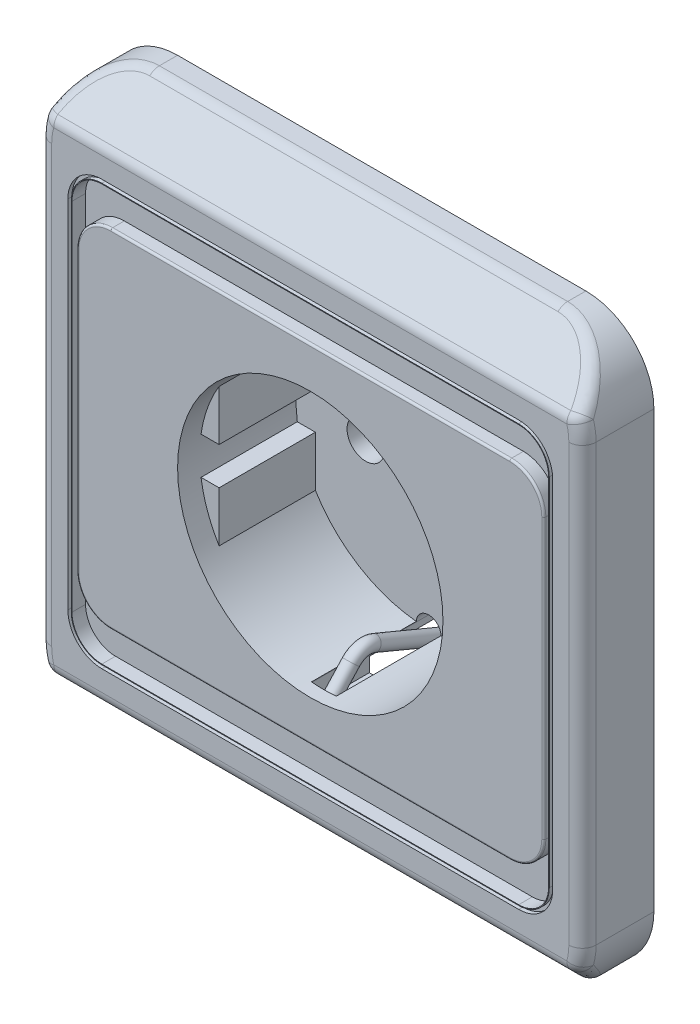
SolidWorks part; units mm, degrees
ref_plane "Ön Düzlem" through (0, 0, 0) normal (0, 0, 1) x (1, 0, 0)
ref_plane "Üst Düzlem" through (0, 0, 0) normal (0, 1, 0) x (1, 0, 0)
ref_plane "Sağ Düzlem" through (0, 0, 0) normal (1, 0, 0) x (0, 0, -1)
sketch "Çizim1" plane through (0, 0, 0) normal (0, 0, 1) x (1, 0, 0)
  line L1 (30, 42) -> (-30, 42)
  line L2 (40, 32) -> (40, -32)
  line L3 (30, -42) -> (-30, -42)
  line L4 (-40, 32) -> (-40, -32)
  line L5 (40, 42) -> (-40, -42) construction
  line L6 (40, -42) -> (-40, 42) construction
  arc A0 (-30, -42) -> (-40, -32) centre (-30, -32) cw
  arc A1 (40, -32) -> (30, -42) centre (30, -32) cw
  arc A2 (30, 42) -> (40, 32) centre (30, 32) cw
  arc A3 (-30, 42) -> (-40, 32) centre (-30, 32) ccw
  point P0 (0, 0)
  dimension "D3" = 10
  dimension "D1" = 84
  dimension "D2" = 80
extrude "Yükseklik-Ekstrüzyon1" add sketch "Çizim1" along normal blind 10.5
sketch "Çizim2" plane through (0, 0, 10.5) normal (0, 0, 1) x (1, 0, 0)
  line L0 (30.625, 30.55) -> (-30.625, 30.55)
  line L1 (30.625, 31.15) -> (-30.625, 31.15)
  line L2 (35.625, 26.15) -> (35.625, -26.15)
  line L3 (30.625, -31.15) -> (-30.625, -31.15)
  line L4 (-35.625, 26.15) -> (-35.625, -26.15)
  line L5 (35.625, 31.15) -> (-35.625, -31.15) construction
  line L6 (35.625, -31.15) -> (-35.625, 31.15) construction
  line L7 (-35.025, 26.15) -> (-35.025, -26.15)
  line L8 (30.625, -30.55) -> (-30.625, -30.55)
  line L9 (35.025, 26.15) -> (35.025, -26.15)
  arc A0 (-30.625, -31.15) -> (-35.625, -26.15) centre (-30.625, -26.15) cw
  arc A1 (35.625, -26.15) -> (30.625, -31.15) centre (30.625, -26.15) cw
  arc A2 (30.625, 31.15) -> (35.625, 26.15) centre (30.625, 26.15) cw
  arc A3 (-30.625, 31.15) -> (-35.625, 26.15) centre (-30.625, 26.15) ccw
  arc A4 (-30.625, 30.55) -> (-35.025, 26.15) centre (-30.625, 26.15) ccw
  arc A5 (-30.625, -30.55) -> (-35.025, -26.15) centre (-30.625, -26.15) cw
  arc A6 (35.025, -26.15) -> (30.625, -30.55) centre (30.625, -26.15) cw
  arc A7 (30.625, 30.55) -> (35.025, 26.15) centre (30.625, 26.15) cw
  point P0 (0, 0)
  dimension "D3" = 5
  dimension "D1" = 62.3
  dimension "D2" = 71.25
  dimension "D4" = 0.6
extrude "Kes-Ekstrüzyon1" cut sketch "Çizim2" against normal blind 0.6
sketch "Çizim3" plane through (0, 0, 10.5) normal (0, 0, 1) x (1, 0, 0)
  line L0 (-35.025, 26.15) -> (-35.025, -26.15) construction
  line L1 (29.325, 25.5) -> (-29.325, 25.5)
  line L2 (34.325, 20.5) -> (34.325, -20.5)
  line L3 (29.325, -25.5) -> (-29.325, -25.5)
  line L4 (-34.325, 20.5) -> (-34.325, -20.5)
  line L5 (34.325, 25.5) -> (-34.325, -25.5) construction
  line L6 (34.325, -25.5) -> (-34.325, 25.5) construction
  line L8 (30.625, 30.55) -> (-30.625, 30.55) construction
  line L9 (30.625, 30.55) -> (-30.625, 30.55)
  line L14 (30.625, 30.55) -> (-30.625, 30.55)
  line L15 (-35.025, 26.15) -> (-35.025, -26.15)
  line L16 (-30.625, -30.55) -> (30.625, -30.55)
  line L17 (35.025, -26.15) -> (35.025, 26.15)
  line L18 (30.625, 30.55) -> (-30.625, 30.55)
  line L19 (-35.025, 26.15) -> (-35.025, -26.15)
  line L20 (-30.625, -30.55) -> (30.625, -30.55)
  line L21 (35.025, -26.15) -> (35.025, 26.15)
  arc A0 (-29.325, -25.5) -> (-34.325, -20.5) centre (-29.325, -20.5) cw
  arc A1 (34.325, -20.5) -> (29.325, -25.5) centre (29.325, -20.5) cw
  arc A2 (29.325, 25.5) -> (34.325, 20.5) centre (29.325, 20.5) cw
  arc A3 (-34.325, 20.5) -> (-29.325, 25.5) centre (-29.325, 20.5) cw
  arc A8 (35.025, 26.15) -> (30.625, 30.55) centre (30.625, 26.15) ccw
  arc A9 (-30.625, 30.55) -> (-35.025, 26.15) centre (-30.625, 26.15) ccw
  arc A10 (-35.025, -26.15) -> (-30.625, -30.55) centre (-30.625, -26.15) ccw
  arc A11 (30.625, -30.55) -> (35.025, -26.15) centre (30.625, -26.15) ccw
  arc A12 (35.025, 26.15) -> (30.625, 30.55) centre (30.625, 26.15) ccw
  arc A13 (-30.625, 30.55) -> (-35.025, 26.15) centre (-30.625, 26.15) ccw
  arc A14 (-35.025, -26.15) -> (-30.625, -30.55) centre (-30.625, -26.15) ccw
  arc A15 (30.625, -30.55) -> (35.025, -26.15) centre (30.625, -26.15) ccw
  point P0 (0, 0)
  arc M9 (35.025, 26.15) -> (30.625, 30.55) centre (30.625, 26.15) ccw
  line M10 (30.625, 30.55) -> (-30.625, 30.55)
  arc M11 (-30.625, 30.55) -> (-35.025, 26.15) centre (-30.625, 26.15) ccw
  line M12 (-35.025, 26.15) -> (-35.025, -26.15)
  arc M13 (-35.025, -26.15) -> (-30.625, -30.55) centre (-30.625, -26.15) ccw
  line M14 (-30.625, -30.55) -> (30.625, -30.55)
  arc M15 (30.625, -30.55) -> (35.025, -26.15) centre (30.625, -26.15) ccw
  line M16 (35.025, -26.15) -> (35.025, 26.15)
  dimension "D3" = 5
  dimension "D1" = 0.7
  dimension "D2" = 51
  dimension "D4" = 0
extrude "Kes-Ekstrüzyon2" cut sketch "Çizim3" against normal blind 2 contours L4 A3 L1 A2 L2 A1 L3 A0 M16 M9 M10 M11 M12 M13 M14 M15 region at (33.079, 28.604, 10.5)
sketch "Çizim4" plane through (0, 0, 10.5) normal (0, 0, 1) x (1, 0, 0)
  circle A0 centre (0, 0) radius 19.5
  dimension "D1" = 39
extrude "Kes-Ekstrüzyon3" cut sketch "Çizim4" against normal blind 51
sketch "Çizim5" plane through (0, 0, 0) normal (0, 0, -1) x (-1, 0, 0)
  circle A0 centre (0, 0) radius 19.5 construction
  circle A1 centre (0, 0) radius 19.5
  circle A2 centre (0, 0) radius 20.5
  dimension "D1" = 1
extrude "Yükseklik-Ekstrüzyon2" add sketch "Çizim5" along normal blind 6.9
sketch "Çizim6" plane through (0, 0, -6.9) normal (0, 0, -1) x (-1, 0, 0)
  circle A1 centre (0, 0) radius 20.5
  circle A2 centre (0, 0) radius 20.5
  dimension "D1" = 0
extrude "Yükseklik-Ekstrüzyon3" add sketch "Çizim6" along normal blind 1
sketch "Çizim7" plane through (0, 0, -6.9) normal (0, 0, 1) x (1, 0, 0)
  line L0 (-16.65, 10.1502) -> (-16.65, 2.75)
  line L1 (-16.65, 2.75) -> (-19.3051, 2.75)
  line L2 (0, 0) -> (0, 14.0864) construction
  line L4 (16.65, 2.75) -> (19.3051, 2.75)
  line L5 (16.65, 10.1502) -> (16.65, 2.75)
  line L6 (-16.65, -2.75) -> (-19.3051, -2.75)
  line L7 (-16.65, -10.1502) -> (-16.65, -2.75)
  line L8 (16.65, -2.75) -> (19.3051, -2.75)
  line L9 (16.65, -10.1502) -> (16.65, -2.75)
  circle A0 centre (0, 0) radius 19.5 construction
  circle A1 centre (0, 0) radius 19.5 construction
  arc A2 (-16.65, 10.1502) -> (-19.3051, 2.75) centre (0, 0) ccw
  arc A3 (16.65, -10.1502) -> (19.3051, -2.75) centre (0, 0) ccw
  arc A4 (19.3051, 2.75) -> (16.65, 10.1502) centre (0, 0) ccw
  arc A5 (-19.3051, -2.75) -> (-16.65, -10.1502) centre (0, 0) ccw
  dimension "D1" = 33.3
extrude "Yükseklik-Ekstrüzyon4" add sketch "Çizim7" along normal blind 14.15
sketch "Çizim8" plane through (0, 0, 10.5) normal (0, 0, 1) x (1, 0, 0)
  line L0 (-1.825, -19.5) -> (-1.825, -22.5)
  line L1 (1.825, -19.5) -> (1.825, -22.5)
  line L2 (1.825, -22.5) -> (-1.825, -22.5)
  line L3 (0, 0) -> (9.3103, 0) construction
  line L4 (0, 0) -> (0, -19.5) construction
  line L5 (1.825, 22.5) -> (-1.825, 22.5)
  line L6 (1.825, 19.5) -> (1.825, 22.5)
  line L7 (-1.825, 19.5) -> (-1.825, 22.5)
  arc A0 (1.825, -19.5) -> (-1.825, -19.5) centre (0, -19.5) ccw
  arc A1 (-16.65, -10.1502) -> (16.65, -10.1502) centre (0, 0) ccw construction
  arc A2 (1.825, 19.5) -> (-1.825, 19.5) centre (0, 19.5) cw
  dimension "D1" = 3.65
  dimension "D2" = 3
extrude "Kes-Ekstrüzyon4" cut sketch "Çizim8" against normal blind 24.15 from offset 2 offset against normal yes
ref_plane "Düzlem1" through (0, 0, 0) normal (-1, 0, 0) x (0, 0, 1)
sketch "Çizim10" plane through (0, 0, 0) normal (-1, 0, 0) x (0, 0, 1)
  line L0 (-8.9, 21.4186) -> (1.161, 17.2265)
  line L1 (4.5224, 17.9644) -> (7.5169, 21.2186)
  line L2 (-7.9, 19.5) -> (-7.9, 17.675) construction
  line L3 (-7.9, 20.4186) -> (0, 20.4186) construction
  arc A0 (1.161, 17.2265) -> (4.5224, 17.9644) centre (2.3148, 19.9958) ccw
  point P9 (3.1, 16.4186)
  dimension "D7" = 3
  dimension "D1" = 1
  dimension "D2" = 1
  dimension "D3" = 110
  dimension "D4" = 5
  dimension "D5" = 12
  dimension "D6" = 4.8
ref_plane "Düzlem2" through (0, 21.2186, 7.5169) normal (0, 0.7359, 0.6771) x (1, 0, 0)
sketch "Çizim11" plane through (0, 21.2186, 7.5169) normal (0, 0.7359, 0.6771) x (1, 0, 0)
  circle A0 centre (0, 0) radius 1
  dimension "D1" = 2
sweep "Süpür1" add profiles "Çizim11" path "Çizim10"
ref_plane "Düzlem3" through (0, 0, 0) normal (0, -1, 0) x (-1, 0, 0)
mirror "Aynalama1" about plane through (0, 0, 0) normal (0, -1, 0) of bodies 109
sketch "Çizim12" plane through (0, 0, -6.9) normal (0, 0, 1) x (1, 0, 0)
  circle A0 centre (9.25, 0) radius 2.75
  circle A1 centre (-9.25, 0) radius 2.75
  point P4 (-6.5, 0)
  point P6 (6.5, 0)
  dimension "D1" = 5.5
  dimension "D2" = 5.5
  dimension "D3" = 13
  dimension "D4" = 6.5
extrude "Kes-Ekstrüzyon5" cut sketch "Çizim12" against normal blind 24.15
sketch "Çizim13" plane through (0, 0, -6.9) normal (0, 0, 1) x (1, 0, 0)
  circle A0 centre (0, 0) radius 2.75
  circle A1 centre (9.25, 0) radius 2.75 construction
extrude "Kes-Ekstrüzyon6" cut sketch "Çizim13" against normal blind 24.15
sketch "Çizim14" plane through (0, 0, -7.9) normal (0, 0, -1) x (-1, 0, 0)
  circle A0 centre (0, 0) radius 2.75 construction
  circle A1 centre (0, 0) radius 2.75 construction
  circle A2 centre (0, 0) radius 3.75
  dimension "D1" = 1
extrude "Yükseklik-Ekstrüzyon5" add sketch "Çizim14" along normal blind 1
sketch "Çizim15" plane through (0, 0, -7.9) normal (0, 0, 1) x (1, 0, 0)
  circle A1 centre (0, 0) radius 2.65
  circle A3 centre (0, 0) radius 2.75 construction
  dimension "D1" = 0.1
extrude "Yükseklik-Ekstrüzyon6" add sketch "Çizim15" along normal blind 1 separate body
fillet "Radyus1" radius 0.7 1 edges at (2.65, 0, -6.9)
sketch "Çizim16" plane through (0, 0, -6.9) normal (0, 0, 1) x (1, 0, 0)
  line L0 (0.25, 0.25) -> (0.25, 2)
  line L1 (0.25, -2) -> (-0.25, -2)
  line L2 (0.25, -2) -> (0.25, -0.25)
  line L3 (0.25, 2) -> (-0.25, 2)
  line L4 (-0.25, -2) -> (-0.25, -0.25)
  line L6 (0.25, -0.25) -> (2, -0.25)
  line L7 (-2, -0.25) -> (-0.25, -0.25)
  line L8 (-2, -0.25) -> (-2, 0.25)
  line L9 (-2, 0.25) -> (-0.25, 0.25)
  line L10 (2, -0.25) -> (2, 0.25)
  line L15 (-0.25, 0.25) -> (-0.25, 2)
  line L18 (0.25, 0.25) -> (2, 0.25)
  point P0 (0, 0)
  point P6 (0, 0)
  dimension "D1" = 4
  dimension "D2" = 0.5
extrude "Kes-Ekstrüzyon7" cut sketch "Çizim16" against normal blind 0.5
chamfer "Pah1" distance 0.2 angle 45 12 edges at (0, 2, -7.4) (0.25, 1.125, -7.4) (1.125, 0.25, -7.4) (2, 0, -7.4) (1.125, -0.25, -7.4) (0.25, -1.125, -7.4) (0, -2, -7.4) (-0.25, -1.125, -7.4) (-1.125, -0.25, -7.4) (-2, 0, -7.4) (-1.125, 0.25, -7.4) (-0.25, 1.125, -7.4)
chamfer "Pah4" distance 7 angle 45 1 edges at (0, 42, 10.5) tangent propagation no
chamfer "Pah6" distance 7 angle 45 1 edges at (0, -42, 10.5) tangent propagation no
fillet "Radyus2" radius 0.3 8 edges at (32.8605, 24.0355, 10.5) (34.325, 0, 10.5) (32.8605, -24.0355, 10.5) (0, -25.5, 10.5) (-32.8605, -24.0355, 10.5) (-34.325, 0, 10.5) (-32.8605, 24.0355, 10.5) (0, 25.5, 10.5)
sketch "Çizim17" plane through (0, 0, 9.9) normal (0, 0, 1) x (1, 0, 0)
  line L0 (-35.125, 26.15) -> (-35.125, -26.15)
  line L1 (-30.625, -30.65) -> (30.625, -30.65)
  line L2 (35.125, -26.15) -> (35.125, 26.15)
  line L3 (30.625, 30.65) -> (-30.625, 30.65)
  line L4 (35.025, -26.15) -> (35.025, 26.15)
  line L5 (-30.625, -30.55) -> (30.625, -30.55)
  line L6 (-35.025, 26.15) -> (-35.025, -26.15)
  line L7 (30.625, 30.55) -> (-30.625, 30.55)
  line L8 (35.025, -26.15) -> (35.025, 26.15)
  line L9 (-30.625, -30.55) -> (30.625, -30.55)
  line L10 (-35.025, 26.15) -> (-35.025, -26.15)
  line L11 (30.625, 30.55) -> (-30.625, 30.55)
  arc A0 (-30.625, 30.65) -> (-35.125, 26.15) centre (-30.625, 26.15) ccw
  arc A1 (-35.125, -26.15) -> (-30.625, -30.65) centre (-30.625, -26.15) ccw
  arc A2 (30.625, -30.65) -> (35.125, -26.15) centre (30.625, -26.15) ccw
  arc A3 (35.125, 26.15) -> (30.625, 30.65) centre (30.625, 26.15) ccw
  arc A4 (35.025, 26.15) -> (30.625, 30.55) centre (30.625, 26.15) ccw
  arc A5 (30.625, -30.55) -> (35.025, -26.15) centre (30.625, -26.15) ccw
  arc A6 (-35.025, -26.15) -> (-30.625, -30.55) centre (-30.625, -26.15) ccw
  arc A7 (-30.625, 30.55) -> (-35.025, 26.15) centre (-30.625, 26.15) ccw
  arc A8 (35.025, 26.15) -> (30.625, 30.55) centre (30.625, 26.15) ccw
  arc A9 (30.625, -30.55) -> (35.025, -26.15) centre (30.625, -26.15) ccw
  arc A10 (-35.025, -26.15) -> (-30.625, -30.55) centre (-30.625, -26.15) ccw
  arc A11 (-30.625, 30.55) -> (-35.025, 26.15) centre (-30.625, 26.15) ccw
  dimension "D1" = 0
  dimension "D2" = 0.1
extrude "Yükseklik-Ekstrüzyon7" add sketch "Çizim17" along normal up to vertex (0.6 mm away) up to point (-35.625, 26.15, 10.5)
fillet "Radyus3" radius 2 14 edges at (-39.8842, 33.5176, 10.5) (-39.8842, -33.5176, 10.5) (39.8842, -33.5176, 10.5) (39.8842, 33.5176, 10.5) (-35.9161, -40.0623, 5.4377) (0, -42, 3.5) (-35.9161, 40.0623, 5.4377) (0, 42, 3.5) (-40, 0, 10.5) (40, 0, 10.5) (35.9161, -40.0623, 5.4377) (0, -35, 10.5) (0, 35, 10.5) (35.9161, 40.0623, 5.4377)
sketch "Çizim19" plane through (0, 0, -7.9) normal (0, 0, -1) x (-1, 0, 0)
  line L4 (1.825, 20.4186) -> (1.825, 19.5)
  line L5 (-1.825, 19.5) -> (-1.825, 20.4186)
  line L6 (-1.825, -20.4186) -> (-1.825, -19.5)
  line L7 (1.825, -19.5) -> (1.825, -20.4186)
  line L8 (1.825, 20.4186) -> (1.825, 19.5)
  line L9 (-1.825, 19.5) -> (-1.825, 20.4186)
  line L10 (-1.825, -20.4186) -> (-1.825, -19.5)
  line L11 (1.825, -19.5) -> (1.825, -20.4186)
  circle A0 centre (-9.25, 0) radius 2.75 construction
  circle A1 centre (9.25, 0) radius 2.75 construction
  circle A2 centre (-9.25, 0) radius 2.75
  circle A3 centre (9.25, 0) radius 2.75
  arc A4 (-1.825, 19.5) -> (1.825, 19.5) centre (0, 19.5) ccw
  arc A5 (-1.825, 20.4186) -> (-1.825, -20.4186) centre (0, 0) ccw
  arc A6 (1.825, -19.5) -> (-1.825, -19.5) centre (0, -19.5) ccw
  arc A7 (1.825, -20.4186) -> (1.825, 20.4186) centre (0, 0) ccw
  arc A8 (-1.825, 19.5) -> (1.825, 19.5) centre (0, 19.5) ccw
  arc A9 (-1.825, 20.4186) -> (-1.825, -20.4186) centre (0, 0) ccw
  arc A10 (1.825, -19.5) -> (-1.825, -19.5) centre (0, -19.5) ccw
  arc A11 (1.825, -20.4186) -> (1.825, 20.4186) centre (0, 0) ccw
  dimension "D1" = 0
extrude "Yükseklik-Ekstrüzyon9" add sketch "Çizim19" along normal blind 5
